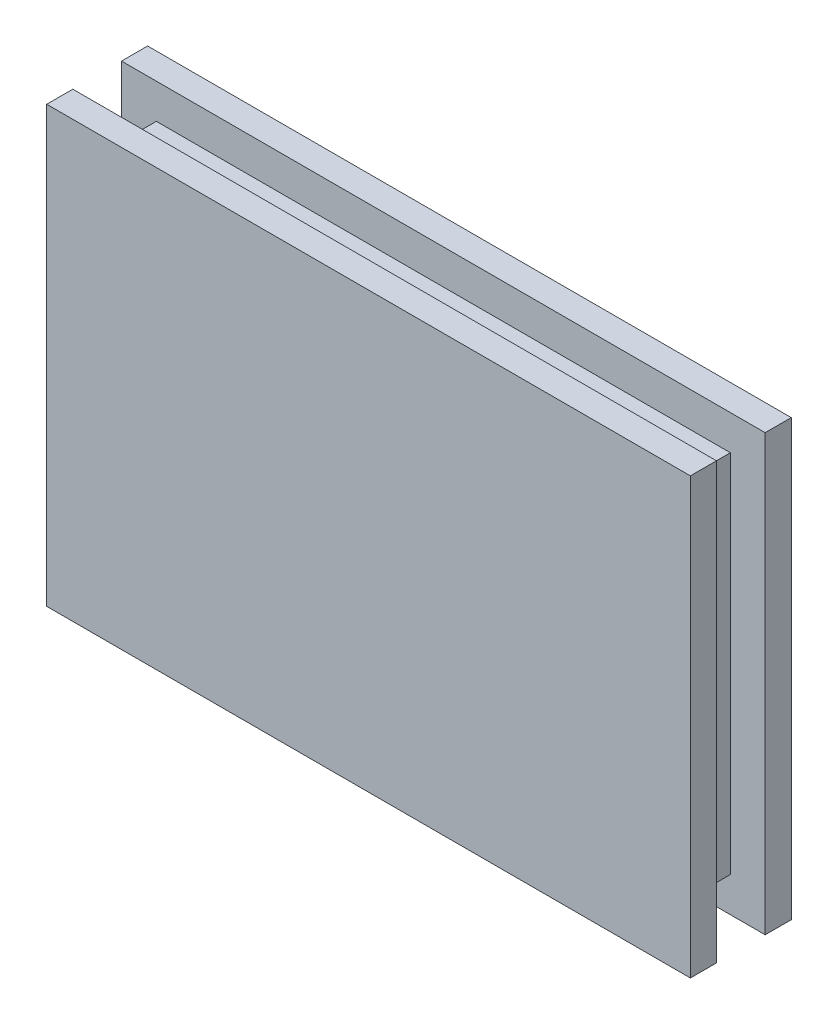
SolidWorks part; units mm, degrees
ref_plane "Alzado" through (0, 0, 0) normal (0, 0, 1) x (1, 0, 0)
ref_plane "Planta" through (0, 0, 0) normal (0, 1, 0) x (1, 0, 0)
ref_plane "Vista lateral" through (0, 0, 0) normal (1, 0, 0) x (0, 0, -1)
sketch "Croquis1" plane through (0, 0, 0) normal (0, 0, 1) x (1, 0, 0)
  line L1 (-18.5, 12.5) -> (18.5, 12.5)
  line L2 (-18.5, 12.5) -> (-18.5, -12.5)
  line L3 (-18.5, -12.5) -> (18.5, -12.5)
  line L4 (18.5, 12.5) -> (18.5, -12.5)
  point P4 (0, 12.5)
  point P6 (-18.5, 0)
  dimension "D1" = 37
  dimension "D2" = 25
extrude "Saliente-Extruir1" add sketch "Croquis1" along normal blind 1.5
sketch "Croquis2" plane through (0, 0, 1.5) normal (0, 0, 1) x (1, 0, 0)
  line L12 (-16.5, 10.5) -> (-16.5, -10.5)
  line L13 (-16.5, -10.5) -> (16.5, -10.5)
  line L14 (16.5, -10.5) -> (16.5, 10.5)
  line L15 (16.5, 10.5) -> (-16.5, 10.5)
  line L16 (-16.5, 10.5) -> (-16.5, -10.5)
  line L17 (-16.5, -10.5) -> (16.5, -10.5)
  line L18 (16.5, -10.5) -> (16.5, 10.5)
  line L19 (16.5, 10.5) -> (-16.5, 10.5)
  dimension "D1" = 2
extrude "Saliente-Extruir2" add sketch "Croquis2" along normal blind 2.8
extrude "Saliente-Extruir3" add sketch "Croquis1<2>" along normal blind 1.5 from surface starting at face at (0, 0, 4.3)
sketch "Croquis1<2>" plane through (0, 0, 0) normal (0, 0, 1) x (1, 0, 0) same geometry as "Croquis1"
